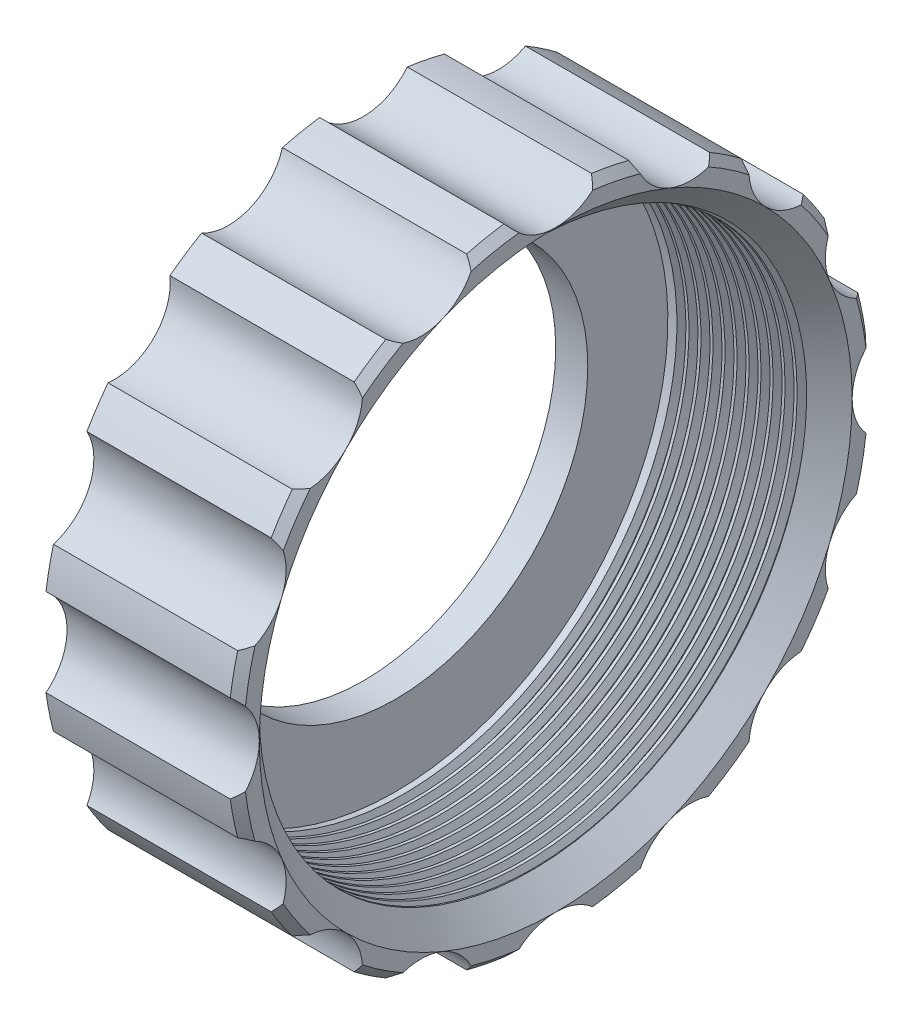
SolidWorks part; units mm, degrees
ref_plane "Front Plane" through (0, 0, 0) normal (0, 0, 1) x (1, 0, 0)
ref_plane "Top Plane" through (0, 0, 0) normal (0, 1, 0) x (1, 0, 0)
ref_plane "Right Plane" through (0, 0, 0) normal (1, 0, 0) x (0, 0, -1)
sketch "Sketch1" plane through (0, 0, 0) normal (0, 0, 1) x (1, 0, 0)
  line L0 (24, 0) -> (-107.7656, 0) construction
  line L1 (0, 0) -> (24, 0)
  line L2 (0, 0) -> (0, 40)
  line L3 (0, 40) -> (24, 40)
  line L4 (24, 0) -> (24, 40)
  dimension "D1" = 40
  dimension "D2" = 24
revolve "Revolve1" add sketch "Sketch1" angle 360 about L0
sketch "Sketch2" plane through (24, 0, 0) normal (1, 0, 0) x (0, 0, -1)
  circle A2 centre (0, 0) radius 34
  circle A3 centre (0, 0) radius 34
  dimension "D1" = 6
extrude "Cut-Extrude1" cut sketch "Sketch2" against normal blind 20
chamfer "Chamfer1" distance 1 angle 45 1 edges at (24, 0, -40)
chamfer "Chamfer2" distance 3 angle 45 1 edges at (24, 0, -34)
sketch "Sketch3" plane through (4, 0, 0) normal (1, 0, 0) x (0, 0, -1)
  circle A2 centre (0, 0) radius 24
  circle A3 centre (0, 0) radius 24
  dimension "D1" = 10
extrude "Cut-Extrude2" cut sketch "Sketch3" against normal through all
thread "Thread2" pitch 1.5 start angle 0, offset 2, length 0, pitch 1.5, diameter 68
ref_plane "Plane3" through (22, 0, 34) normal (0, -1, 0) x (0, 0, 1)
sketch "Thread Profile3" plane through (22, 0, 34) normal (0, -1, 0) x (0, 0, 1)
  line L0 (0, 0) -> (0, 1.5) construction
  line L1 (0, 0) -> (0.8119, 0.4687)
  line L2 (0.8119, 0.4687) -> (0.8119, 0.6562)
  line L3 (0.8119, 0.6562) -> (0, 1.125)
  line L4 (0.8119, 0.5625) -> (0, 0.5625) construction
  line L11 (0, 0) -> (0, 1.125)
  point P2 (0, 0)
  dimension "Pitch" = 1.5
  dimension "Profile_Angle" = 60
  dimension "Profile_Land" = 0.1875
  dimension "Profile_Height" = 0.8119
sketch "Sketch13" plane through (24, 0, 0) normal (1, 0, 0) x (0, 0, -1)
  line L0 (-72.6298, 0) -> (61.7532, 0) construction
  line L1 (0, -55.1582) -> (0, 53.3453) construction
  circle A0 centre (0, 0) radius 44 construction
  circle A1 centre (0, 44) radius 7
  dimension "D1" = 88
  dimension "D2" = 14
extrude "Cut-Extrude3" cut sketch "Sketch13" against normal through all and the other way through all
pattern_circular "CirPattern1" count 16 over 360 about axis through (0, 0, 0) along (1, 0, 0) of "Cut-Extrude3"
equation "\"mm2mm\"=0.5"
